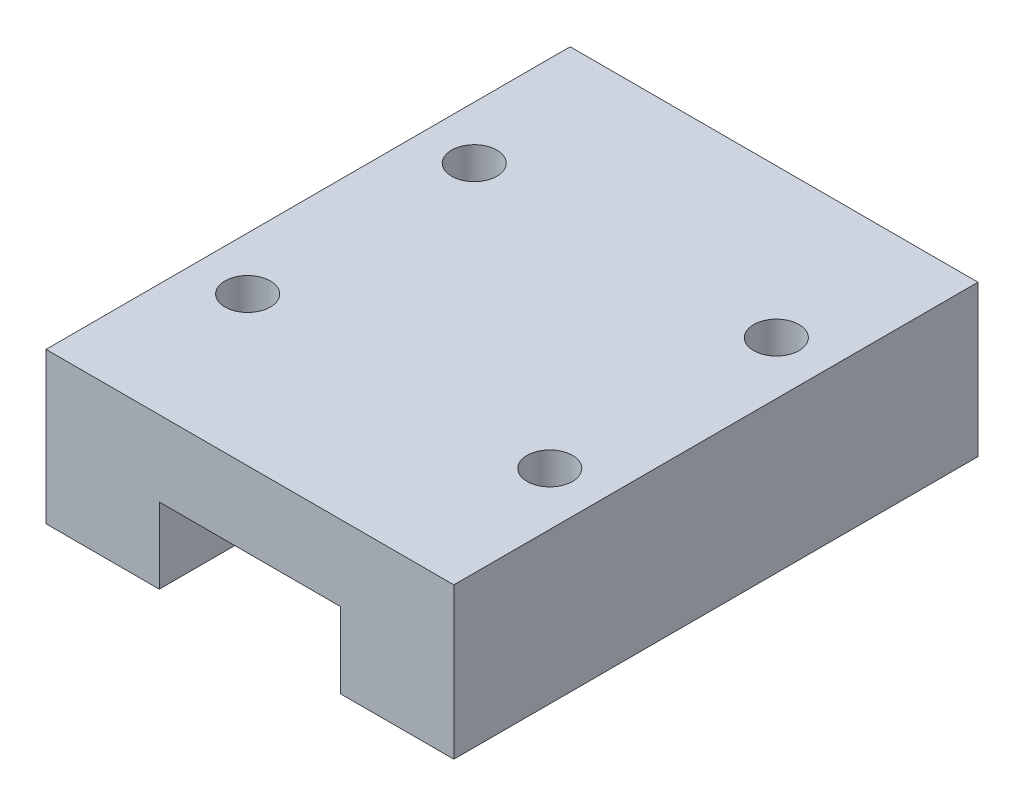
SolidWorks part; units mm, degrees
ref_plane "前视基准面" through (0, 0, 0) normal (0, 0, 1) x (1, 0, 0)
ref_plane "上视基准面" through (0, 0, 0) normal (0, 1, 0) x (1, 0, 0)
ref_plane "右视基准面" through (0, 0, 0) normal (1, 0, 0) x (0, 0, -1)
sketch "草图2" plane through (0, 0, 0) normal (0, 0, 1) x (1, 0, 0)
  line L1 (13.5, -5) -> (-13.5, -5)
  line L2 (13.5, -5) -> (13.5, 5)
  line L3 (13.5, 5) -> (-13.5, 5)
  line L4 (-13.5, -5) -> (-13.5, 5)
  line L5 (13.5, -5) -> (-13.5, 5) construction
  line L6 (13.5, 5) -> (-13.5, -5) construction
  line L7 (-6, 0) -> (6, 0)
  line L8 (-6, 0) -> (-6, -5)
  line L9 (-6, -5) -> (6, -5)
  line L10 (6, 0) -> (6, -5)
  line L11 (-6, 0) -> (6, -5) construction
  line L12 (-6, -5) -> (6, 0) construction
  point P0 (0, 0)
  point P6 (0, -2.5)
  dimension "D1" = 27
  dimension "D2" = 10
  dimension "D3" = 12
  dimension "D4" = 5
extrude "凸台-拉伸1" add sketch "草图2" along normal blind 34.7 contours L7 L10 L1 L2 L3 L4 L8 region at (0, 0.7143, 0)
sketch "草图3" plane through (0, 5, 0) normal (0, 1, 0) x (1, 0, 0)
  line L0 (-13.5, 0) -> (13.5, -34.7) construction
  line L2 (-10, -24.85) -> (10, -24.85) construction
  line L3 (-10, -24.85) -> (-10, -9.85) construction
  line L4 (-10, -9.85) -> (10, -9.85) construction
  line L5 (10, -24.85) -> (10, -9.85) construction
  line L6 (-10, -24.85) -> (10, -9.85) construction
  line L7 (-10, -9.85) -> (10, -24.85) construction
  circle A0 centre (-10, -9.85) radius 1.5
  circle A1 centre (10, -9.85) radius 1.5
  circle A2 centre (10, -24.85) radius 1.5
  circle A3 centre (-10, -24.85) radius 1.5
  point P4 (0, -17.35)
  dimension "D3" = 3
  dimension "D4" = 3
  dimension "D5" = 3
  dimension "D6" = 3
  dimension "D1" = 15
  dimension "D2" = 20
extrude "切除-拉伸1" cut sketch "草图3" against normal blind 3.5
